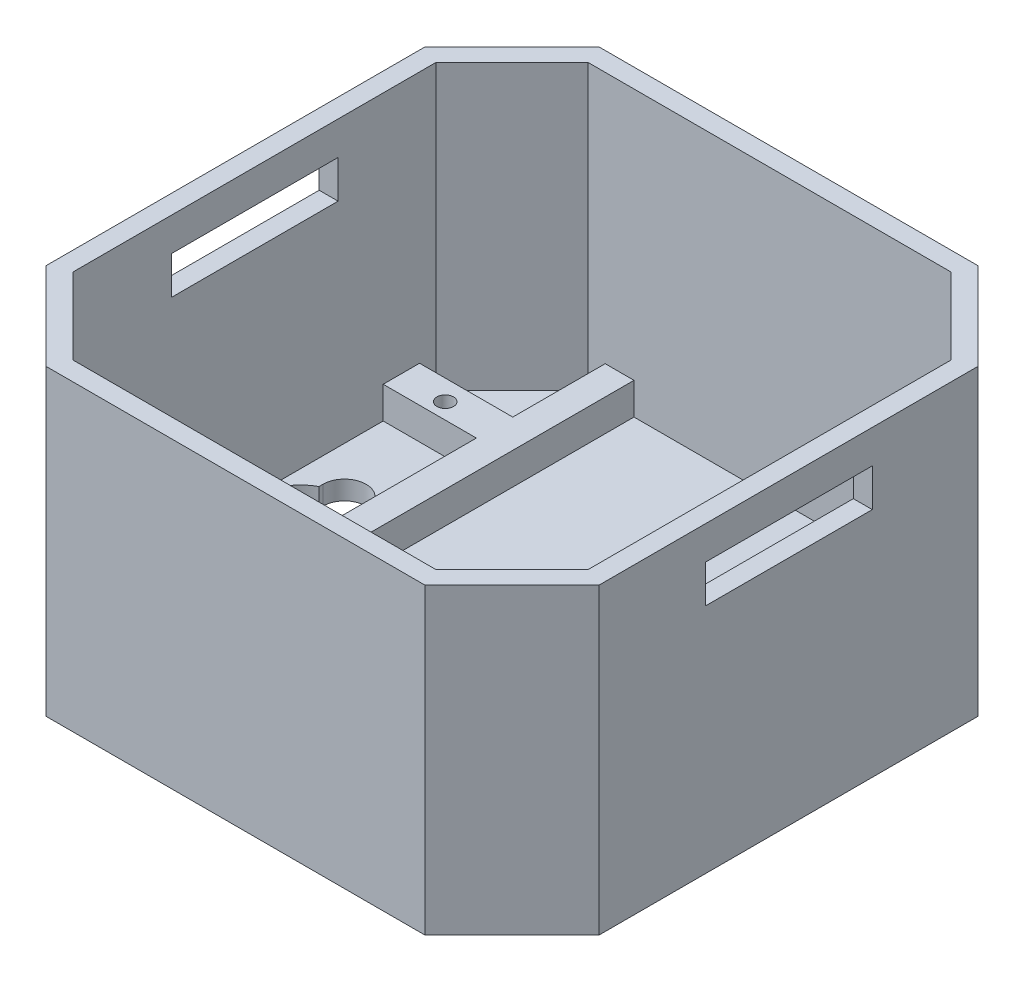
SolidWorks part; units mm, degrees
ref_plane "Alzado" through (0, 0, 0) normal (0, 0, 1) x (1, 0, 0)
ref_plane "Planta" through (0, 0, 0) normal (0, 1, 0) x (1, 0, 0)
ref_plane "Vista lateral" through (0, 0, 0) normal (1, 0, 0) x (0, 0, -1)
sketch "Croquis3" plane through (0, 0, 0) normal (0, 1, 0) x (1, 0, 0)
  line L0 (-25, -32.5) -> (25, -32.5) construction
  line L1 (-25, 32.5) -> (25, 32.5) construction
  line L2 (-25, -32.5) -> (25, 32.5) construction
  line L3 (-25, 32.5) -> (25, -32.5) construction
  line L4 (32.5, 25) -> (32.5, -25) construction
  line L5 (25, -32.5) -> (32.5, -25) construction
  line L6 (32.5, 25) -> (25, 32.5) construction
  line L7 (-32.5, 25) -> (-32.5, -25) construction
  line L8 (-32.5, -25) -> (-25, -32.5) construction
  line L9 (-32.5, 25) -> (-25, 32.5) construction
  line L10 (-25, -32.5) -> (-25, -36.5) construction
  line L11 (-32.5, -25) -> (-36.5, -25) construction
  line L12 (-32.5, 25) -> (-36.5, 25) construction
  line L13 (-25, 32.5) -> (-25, 36.5)
  line L14 (25, 32.5) -> (25, 36.5) construction
  line L15 (32.5, 25) -> (36.5, 25) construction
  line L16 (32.5, -25) -> (36.5, -25) construction
  line L17 (25, -32.5) -> (25, -36.5) construction
  line L18 (-25, -36.5) -> (25, -36.5)
  line L19 (36.5, -25) -> (36.5, 25)
  line L20 (25, 36.5) -> (-25, 36.5)
  line L21 (-36.5, 25) -> (-36.5, -25)
  line L22 (-36.5, -25) -> (-25, -36.5)
  line L23 (-36.5, 25) -> (-25, 36.5)
  line L24 (25, 36.5) -> (36.5, 25)
  line L25 (25, -36.5) -> (36.5, -25)
  point P0 (0, 0)
  point P5 (0, 32.5)
  dimension "D1" = 65
  dimension "D2" = 50
  dimension "D3" = 50
  dimension "D4" = 25
  dimension "D5" = 25
  dimension "D6" = 4
  dimension "D8" = 4
  dimension "D10" = 4
extrude "Saliente-Extruir1" add sketch "Croquis3" along normal blind 40 contours L18 L25 L19 L24 L20 L1 L6 L4 L5 L0 L8 L7 L9 L23 L21 L22 region at (0, 0, 0)
shell "Vaciado1" thickness 2.5 removed face at (0, 40, 0)
sketch "Croquis5" plane through (-36.5, 0, 0) normal (-1, 0, 0) x (0, 0, 1)
  line L0 (-25, 40) -> (-25, 0) construction
  line L1 (-11.05, 35.6) -> (10.95, 35.6)
  line L2 (-11.05, 35.6) -> (-11.05, 30.6)
  line L3 (-11.05, 30.6) -> (10.95, 30.6)
  line L4 (10.95, 35.6) -> (10.95, 30.6)
  dimension "D1" = 22
  dimension "D2" = 13.95
  dimension "D3" = 4.4
  dimension "D4" = 5
extrude "Cortar-Extruir1" cut sketch "Croquis5" against normal through all
sketch "Croquis6" plane through (0, 0, 0) normal (0, -1, 0) x (1, 0, 0)
  line L0 (-36.5, 0) -> (-27.9, 0) construction
  line L1 (-36.5, -25) -> (-36.5, 25) construction
  line L2 (0, 0) -> (0, 10.1817) construction
  line L3 (27.9, -5.8) -> (27.9, -6.5543) construction
  line L4 (-30.75, -5.8) -> (-30.75, -5.2799)
  line L5 (-27.9, -5.8) -> (-27.9, -6.5543) construction
  line L6 (-25.05, -5.8) -> (-25.05, -5.2799)
  line L7 (36.5, 0) -> (27.9, 0) construction
  line L8 (25.05, -5.8) -> (25.05, -5.2799)
  line L9 (30.75, -5.8) -> (30.75, -5.2799)
  arc A0 (-25.05, -5.2799) -> (-30.75, -5.2799) centre (-27.9, 0) ccw
  arc A1 (-30.75, -5.8) -> (-25.05, -5.8) centre (-27.9, -5.8) ccw
  arc A2 (30.75, -5.8) -> (25.05, -5.8) centre (27.9, -5.8) cw
  arc A3 (25.05, -5.2799) -> (30.75, -5.2799) centre (27.9, 0) cw
  point P8 (-27.9, -8.65)
  point P22 (27.9, -8.65)
  dimension "D2" = 12
  dimension "D4" = 5.7
  dimension "D1" = 8.6
  dimension "D3" = 5.8
extrude "Cortar-Extruir2" cut sketch "Croquis6" against normal blind 10
sketch "Croquis7" plane through (0, 2.5, 0) normal (0, 1, 0) x (1, 0, 0)
  line L0 (-33.9, 0) -> (-21.7, 0) construction
  line L1 (-33.9, 0) -> (-17.9, 0) construction
  line L2 (-21.7, 0) -> (-21.7, 17)
  line L3 (23.9645, 34) -> (-23.9645, 34) construction
  line L4 (-21.7, 0) -> (-21.7, -6)
  line L5 (-23.9645, -34) -> (23.9645, -34) construction
  line L6 (-17.9, -34) -> (-17.9, 34)
  line L7 (-23.9645, -34) -> (23.9645, -34) construction
  line L8 (-17.9, 34) -> (-21.7, 34)
  line L9 (-21.7, -34) -> (-17.9, -34)
  line L10 (-27.9, -6) -> (-27.9, 16.7) construction
  line L11 (-21.7, 17) -> (-34, 17)
  line L12 (-34, 23.9645) -> (-34, -23.9645) construction
  line L13 (-21.7, 21.8) -> (-34, 21.8)
  line L14 (-34, 21.8) -> (-34, 17)
  line L15 (-21.7, -6) -> (-34, -6)
  line L16 (-21.7, -10.8) -> (-34, -10.8)
  line L17 (-34, 23.9645) -> (-34, -23.9645) construction
  line L18 (-34, -6) -> (-34, -10.8)
  line L19 (-21.7, 21.8) -> (-21.7, 34)
  line L20 (-21.7, -10.8) -> (-21.7, -15.8)
  line L21 (0, 0) -> (0, 8.7272) construction
  line L22 (27.9, -6) -> (27.9, 16.7) construction
  line L23 (33.9, 0) -> (17.9, 0) construction
  line L24 (33.9, 0) -> (21.7, 0) construction
  line L25 (21.7, -19.8) -> (21.7, -34)
  line L26 (34, -15.8) -> (34, -19.8)
  line L27 (21.7, -19.8) -> (34, -19.8)
  line L28 (34, -15.8) -> (21.7, -15.8)
  line L29 (21.7, -10.8) -> (21.7, -15.8)
  line L30 (21.7, 21.8) -> (21.7, 34)
  line L31 (34, -6) -> (34, -10.8)
  line L32 (21.7, -10.8) -> (34, -10.8)
  line L33 (21.7, -6) -> (34, -6)
  line L34 (34, 21.8) -> (34, 17)
  line L35 (21.7, 21.8) -> (34, 21.8)
  line L36 (21.7, 17) -> (34, 17)
  line L37 (21.7, -34) -> (17.9, -34)
  line L38 (-34, -15.8) -> (-21.7, -15.8)
  line L39 (-34, -19.8) -> (-34, -23.9645)
  line L40 (-34, -15.8) -> (-34, -19.8)
  line L41 (-34, -23.9645) -> (-23.9645, -34)
  line L42 (17.9, 34) -> (21.7, 34)
  line L43 (17.9, -34) -> (17.9, 34)
  line L44 (21.7, 0) -> (21.7, -6)
  line L45 (21.7, 0) -> (21.7, 17)
  line L46 (-23.9645, -34) -> (-21.7, -34)
  arc A0 (-30.75, 5.2799) -> (-25.05, 5.2799) centre (-27.9, 0) ccw construction
  dimension "D1" = 12.2
  dimension "D2" = 16
  dimension "D3" = 22.7
  dimension "D4" = 4.8
  dimension "D5" = 4.8
  dimension "D6" = 5
  dimension "D7" = 4
extrude "Saliente-Extruir4" add sketch "Croquis7" along normal blind 4.2
sketch "Croquis9" plane through (0, 2.5, 0) normal (0, 1, 0) x (1, 0, 0)
  line L0 (0, 0) -> (0, 6.8473) construction
  line L1 (-21.7, -10.8) -> (-34, -10.8)
  line L2 (-21.7, -10.8) -> (-21.7, -15.8)
  line L3 (-21.7, -15.8) -> (-34, -15.8)
  line L4 (-34, -10.8) -> (-34, -15.8)
  line L5 (34, -10.8) -> (34, -15.8)
  line L6 (21.7, -15.8) -> (34, -15.8)
  line L7 (21.7, -10.8) -> (21.7, -15.8)
  line L8 (21.7, -10.8) -> (34, -10.8)
extrude "Cortar-Extruir3" cut sketch "Croquis9" against normal through all
sketch "Croquis10" plane through (0, 6.7, 0) normal (0, 1, 0) x (1, 0, 0)
  circle A0 centre (-24.9, -22.8) radius 6
  dimension "D1" = 12
  dimension "D2" = 7
  dimension "D3" = 7
extrude "Cortar-Extruir4" cut sketch "Croquis10" against normal blind 4
sketch "Croquis11" plane through (0, 2.7, 0) normal (0, 1, 0) x (1, 0, 0)
  circle A0 centre (-24.9, -22.8) radius 2.75
  dimension "D1" = 5.5
extrude "Cortar-Extruir5" cut sketch "Croquis11" against normal blind 4
sketch "Croquis12" plane through (0, 6.7, 0) normal (0, 1, 0) x (1, 0, 0)
  line L0 (-34, 23.9645) -> (-34, -23.9645) construction
  line L1 (0, 0) -> (0, 8.3797) construction
  circle A0 centre (-27.91, 19.1) radius 1.1
  circle A1 centre (-27.91, -8.7) radius 1.1
  circle A2 centre (27.91, -8.7) radius 1.1
  circle A3 centre (27.91, 19.1) radius 1.1
  dimension "D3" = 2.2
  dimension "D5" = 2.2
  dimension "D1" = 6.09
  dimension "D2" = 2.7
  dimension "D4" = 2.7
  dimension "D6" = 6.09
extrude "Cortar-Extruir6" cut sketch "Croquis12" against normal blind 6
